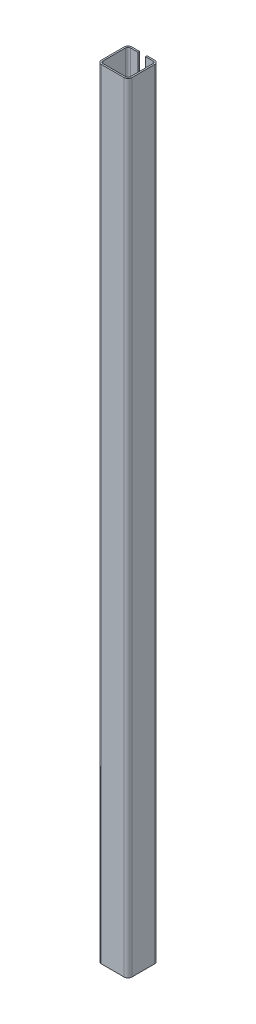
SolidWorks part; units mm, degrees
ref_plane "Спереди" through (0, 0, 0) normal (0, 0, 1) x (1, 0, 0)
ref_plane "Сверху" through (0, 0, 0) normal (0, 1, 0) x (1, 0, 0)
ref_plane "Справа" through (0, 0, 0) normal (1, 0, 0) x (0, 0, -1)
sketch "Эскиз1" plane through (0, 0, 0) normal (0, 1, 0) x (1, 0, 0)
  line L0 (-15, 0) -> (15, 0)
  line L1 (20, 5) -> (20, 35)
  line L2 (5, 40) -> (15, 40)
  line L3 (-20, 5) -> (-20, 35)
  line L4 (-15, 40) -> (-5, 40)
  arc A0 (-20, 35) -> (-15, 40) centre (-15, 35) cw
  arc A1 (20, 35) -> (15, 40) centre (15, 35) ccw
  arc A2 (15, 0) -> (20, 5) centre (15, 5) ccw
  arc A3 (-15, 0) -> (-20, 5) centre (-15, 5) cw
  dimension "D1" = 5
extrude "Вытянуть-Тонкостенный1" add sketch "Эскиз1" along normal blind 1025 thin thin type one direction wall 2
